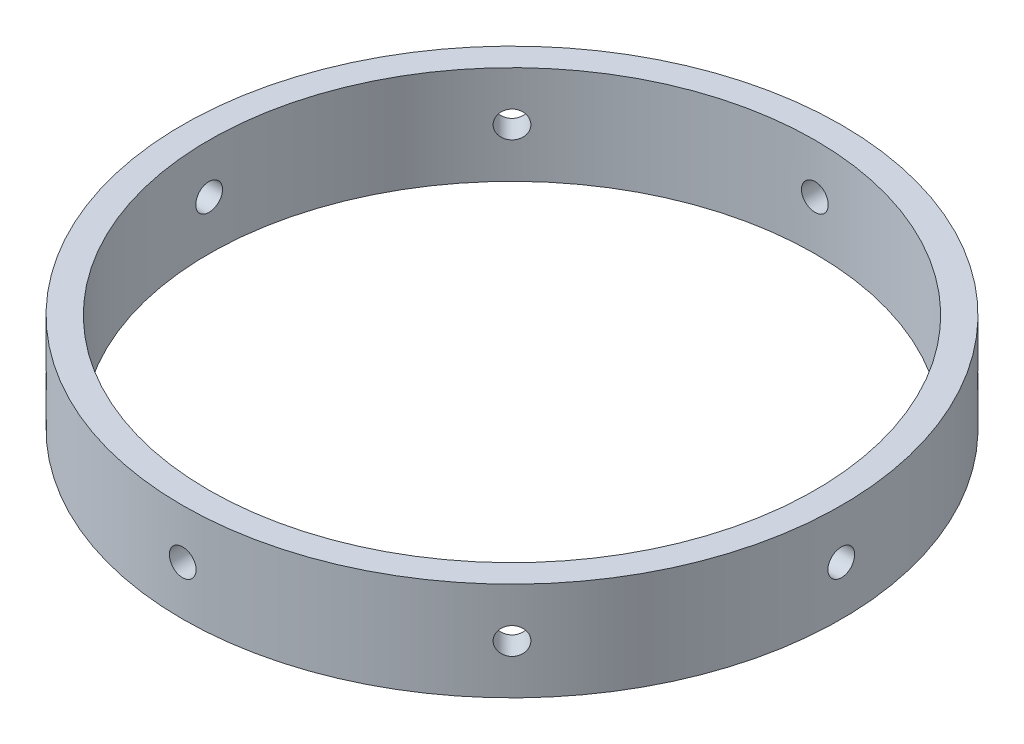
SolidWorks part; units mm, degrees
ref_plane "Front Plane" through (0, 0, 0) normal (0, 0, 1) x (1, 0, 0)
ref_plane "Top Plane" through (0, 0, 0) normal (0, 1, 0) x (1, 0, 0)
ref_plane "Right Plane" through (0, 0, 0) normal (1, 0, 0) x (0, 0, -1)
sketch "Sketch3" plane through (0, 0, 0) normal (0, 1, 0) x (1, 0, 0)
  circle A0 centre (0, 0) radius 46.85
  circle A1 centre (0, 0) radius 43.1
  dimension "D1" = 93.7
  dimension "D2" = 86.2
extrude "Boss-Extrude1" add sketch "Sketch3" along normal blind 14
ref_plane "Plane2" through (46.85, 0, 0) normal (1, 0, 0) x (0, 0, -1)
sketch "Sketch5" plane through (46.85, 0, 0) normal (1, 0, 0) x (0, 0, -1)
  line L0 (0, 0) -> (0, 14) construction
  line L1 (43.1, 14) -> (-43.1, 14) construction
  line L2 (-55.8566, 10) -> (-56.1948, 10) construction
  line L3 (-56.1948, 10) -> (55.6312, 10) construction
  circle A0 centre (0, 7) radius 1.9
  dimension "D1" = 3.8
extrude "Cut-Extrude1" cut sketch "Sketch5" against normal up to next
pattern_circular "CirPattern1" count 8 over 360 about axis through (0, 14, 0) along (0, -1, 0) of "Cut-Extrude1" reverse direction yes
equation "\"circulo grande\"= 93.70mm"
equation "\"D1@Sketch3\"=\"circulo grande\""
equation "\"circulo pequeño\"= 86.20mm"
equation "\"D2@Sketch3\"=\"circulo pequeño\""
equation "\"ancho\"= 1.4cm"
equation "\"Boss-Extrude1@Boss-Extrude1\"=\"ancho\""
equation "\"circulo tornillo\"= 3.8mm"
equation "\"D1@Sketch5\"=\"circulo tornillo\""
